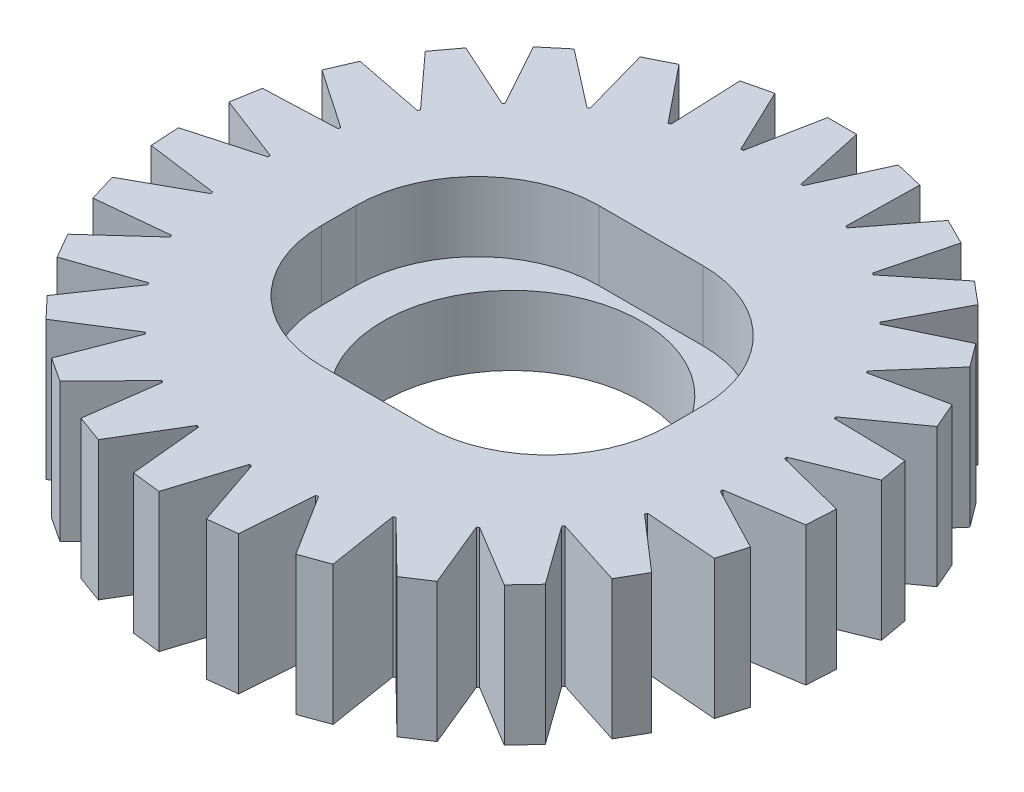
SolidWorks part; units mm, degrees
ref_plane "Front Plane" through (0, 0, 0) normal (0, 0, 1) x (1, 0, 0)
ref_plane "Top Plane" through (0, 0, 0) normal (0, 1, 0) x (1, 0, 0)
ref_plane "Right Plane" through (0, 0, 0) normal (1, 0, 0) x (0, 0, -1)
sketch "Sketch2" plane through (0, 0, 0) normal (0, 1, 0) x (1, 0, 0)
  line L0 (0, 7.5) -> (0, -22.3339) construction
  line L1 (7.5, 0) -> (-25.2541, 0) construction
  circle A0 centre (0, 0) radius 7.5
  dimension "D1" = 15
extrude "Boss-Extrude1" add sketch "Sketch2" along normal blind 4
sketch "Sketch3" plane through (0, 4, 0) normal (0, 1, 0) x (1, 0, 0)
  line L1 (-5, 4) -> (5, 4)
  line L2 (-5, 4) -> (-5, -4)
  line L3 (-5, -4) -> (5, -4)
  line L4 (5, 4) -> (5, -4)
  line L5 (-5, 4) -> (5, -4) construction
  line L6 (-5, -4) -> (5, 4) construction
  point P0 (0, 0)
  dimension "D1" = 10
  dimension "D2" = 8
extrude "Cut-Extrude1" cut sketch "Sketch3" against normal blind 2
fillet "Fillet1" radius 3.5 4 edges at (-5, 3, 4) (5, 3, 4) (-5, 3, -4) (5, 3, -4)
sketch "Sketch4" plane through (0, 2, 0) normal (0, 1, 0) x (1, 0, 0)
  line L1 (1.5, 4) -> (-1.5, 4) construction
  line L2 (0, 0) -> (0, -17.2909) construction
  circle A0 centre (0, 0) radius 3.725
  dimension "D1" = 7.45
  dimension "D3" = 4
extrude "Cut-Extrude2" cut sketch "Sketch4" against normal through all
ref_plane "Plane1" through (0, 4, 0) normal (0, 1, 0) x (1, 0, 0)
sketch "Sketch5" plane through (0, 4, 0) normal (0, 1, 0) x (1, 0, 0)
  line L0 (0, 0) -> (0, 13.0768) construction
  line L1 (0, 0) -> (17.6113, 0) construction
  line L2 (-0.7986, 7.4367) -> (-0.3997, 9.4923)
  line L3 (-0.3997, 9.4923) -> (0.4369, 9.4923)
  line L4 (0.4369, 9.4923) -> (0.8817, 7.4367)
  line L5 (0.8817, 7.4367) -> (-0.7986, 7.4367)
  line L6 (2.6142, 9.1356) -> (2.573, 7.0329)
  line L7 (0.938, 7.4204) -> (1.8001, 9.3286)
  line L8 (1.8001, 9.3286) -> (2.6142, 9.1356)
  line L9 (2.573, 7.0329) -> (0.938, 7.4204)
  line L10 (4.6505, 8.2865) -> (4.1255, 6.25)
  line L11 (2.624, 7.0041) -> (3.9029, 8.662)
  line L12 (3.9029, 8.662) -> (4.6505, 8.2865)
  line L13 (4.1255, 6.25) -> (2.624, 7.0041)
  line L14 (6.4362, 6.9907) -> (5.4557, 5.1301)
  line L15 (4.1685, 6.2102) -> (5.7953, 7.5284)
  line L16 (5.7953, 7.5284) -> (6.4362, 6.9907)
  line L17 (5.4557, 5.1301) -> (4.1685, 6.2102)
  line L18 (7.8748, 5.318) -> (6.4917, 3.7336)
  line L19 (5.4883, 5.0814) -> (7.3753, 5.989)
  line L20 (7.3753, 5.989) -> (7.8748, 5.318)
  line L21 (6.4917, 3.7336) -> (5.4883, 5.0814)
  line L22 (8.889, 3.3586) -> (7.1777, 2.1359)
  line L23 (6.5122, 3.6788) -> (8.5576, 4.1267)
  line L24 (8.5576, 4.1267) -> (8.889, 3.3586)
  line L25 (7.1777, 2.1359) -> (6.5122, 3.6788)
  line L26 (9.4239, 1.2181) -> (7.4768, 0.423)
  line L27 (7.1851, 2.0778) -> (9.2786, 2.042)
  line L28 (9.2786, 2.042) -> (9.4239, 1.2181)
  line L29 (7.4768, 0.423) -> (7.1851, 2.0778)
  line L30 (9.4508, -0.9881) -> (7.3729, -1.3126)
  line L31 (7.4706, 0.3648) -> (9.4994, -0.1529)
  line L32 (9.4994, -0.1529) -> (9.4508, -0.9881)
  line L33 (7.3729, -1.3126) -> (7.4706, 0.3648)
  line L34 (8.9682, -3.1409) -> (6.8714, -2.9776)
  line L35 (7.3533, -1.3679) -> (9.2081, -2.3395)
  line L36 (9.2081, -2.3395) -> (8.9682, -3.1409)
  line L37 (6.8714, -2.9776) -> (7.3533, -1.3679)
  line L38 (8.0021, -5.1245) -> (5.9995, -4.482)
  line L39 (6.8397, -3.0268) -> (8.4204, -4.4)
  line L40 (8.4204, -4.4) -> (8.0021, -5.1245)
  line L41 (5.9995, -4.482) -> (6.8397, -3.0268)
  line L42 (6.6046, -6.8318) -> (4.8042, -5.7447)
  line L43 (5.9573, -4.5225) -> (7.1787, -6.2232)
  line L44 (7.1787, -6.2232) -> (6.6046, -6.8318)
  line L45 (4.8042, -5.7447) -> (5.9573, -4.5225)
  line L46 (4.8511, -8.1707) -> (3.3499, -6.6978)
  line L47 (4.7537, -5.7745) -> (5.55, -7.711)
  line L48 (5.55, -7.711) -> (4.8511, -8.1707)
  line L49 (3.3499, -6.6978) -> (4.7537, -5.7745)
  line L50 (2.836, -9.0692) -> (1.715, -7.2898)
  line L51 (3.2939, -6.7151) -> (3.6222, -8.7831)
  line L52 (3.6222, -8.7831) -> (2.836, -9.0692)
  line L53 (1.715, -7.2898) -> (3.2939, -6.7151)
  line L54 (0.6681, -9.4788) -> (-0.0124, -7.4888)
  line L55 (1.6565, -7.2937) -> (1.499, -9.3817)
  line L56 (1.499, -9.3817) -> (0.6681, -9.4788)
  line L57 (-0.0124, -7.4888) -> (1.6565, -7.2937)
  line L58 (-1.5359, -9.3774) -> (-1.7391, -7.2841)
  line L59 (-0.0702, -7.4791) -> (-0.705, -9.4745)
  line L60 (-0.705, -9.4745) -> (-1.5359, -9.3774)
  line L61 (-1.7391, -7.2841) -> (-0.0702, -7.4791)
  line L62 (-3.6571, -8.7704) -> (-3.3721, -6.6866)
  line L63 (-1.7931, -7.2613) -> (-2.8709, -9.0565)
  line L64 (-2.8709, -9.0565) -> (-3.6571, -8.7704)
  line L65 (-3.3721, -6.6866) -> (-1.7931, -7.2613)
  line L66 (-5.5811, -7.6906) -> (-4.8232, -5.7288)
  line L67 (-3.4193, -6.6521) -> (-4.8821, -8.1503)
  line L68 (-4.8821, -8.1503) -> (-5.5811, -7.6906)
  line L69 (-4.8232, -5.7288) -> (-3.4193, -6.6521)
  line L70 (-7.2042, -6.1962) -> (-6.0143, -4.462)
  line L71 (-4.8613, -5.6842) -> (-6.6301, -6.8047)
  line L72 (-6.6301, -6.8047) -> (-7.2042, -6.1962)
  line L73 (-6.0143, -4.462) -> (-4.8613, -5.6842)
  line L74 (-8.439, -4.3678) -> (-6.8812, -2.9548)
  line L75 (-6.0411, -4.4099) -> (-8.0207, -5.0923)
  line L76 (-8.0207, -5.0923) -> (-8.439, -4.3678)
  line L77 (-6.8812, -2.9548) -> (-6.0411, -4.4099)
  line L78 (-9.2188, -2.3039) -> (-7.3772, -1.2882)
  line L79 (-6.8953, -2.8979) -> (-8.9788, -3.1053)
  line L80 (-8.9788, -3.1053) -> (-9.2188, -2.3039)
  line L81 (-7.3772, -1.2882) -> (-6.8953, -2.8979)
  line L82 (-9.5016, -0.1158) -> (-7.4754, 0.4478)
  line L83 (-7.3777, -1.2296) -> (-9.453, -0.951)
  line L84 (-9.453, -0.951) -> (-9.5016, -0.1158)
  line L85 (-7.4754, 0.4478) -> (-7.3777, -1.2296)
  line L86 (-9.2722, 2.0785) -> (-7.1706, 2.1597)
  line L87 (-7.4624, 0.5049) -> (-9.4175, 1.2547)
  line L88 (-9.4175, 1.2547) -> (-9.2722, 2.0785)
  line L89 (-7.1706, 2.1597) -> (-7.4624, 0.5049)
  line L90 (-8.5429, 4.1608) -> (-6.4793, 3.7551)
  line L91 (-7.1448, 2.2123) -> (-8.8743, 3.3927)
  line L92 (-8.8743, 3.3927) -> (-8.5429, 4.1608)
  line L93 (-6.4793, 3.7551) -> (-7.1448, 2.2123)
  line L94 (-7.3531, 6.0188) -> (-5.4386, 5.1481)
  line L95 (-6.442, 3.8003) -> (-7.8527, 5.3478)
  line L96 (-7.8527, 5.3478) -> (-7.3531, 6.0188)
  line L97 (-5.4386, 5.1481) -> (-6.442, 3.8003)
  line L98 (-5.7668, 7.5523) -> (-4.1048, 6.2636)
  line L99 (-5.392, 5.1835) -> (-6.4077, 7.0146)
  line L100 (-6.4077, 7.0146) -> (-5.7668, 7.5523)
  line L101 (-4.1048, 6.2636) -> (-5.392, 5.1835)
  line L102 (-3.8697, 8.6787) -> (-2.5496, 7.0414)
  line L103 (-4.0512, 6.2873) -> (-4.6173, 8.3032)
  line L104 (-4.6173, 8.3032) -> (-3.8697, 8.6787)
  line L105 (-2.5496, 7.0414) -> (-4.0512, 6.2873)
  line L106 (-1.764, 9.3371) -> (-0.8571, 7.4396)
  line L107 (-2.4921, 7.0521) -> (-2.578, 9.1442)
  line L108 (-2.578, 9.1442) -> (-1.764, 9.3371)
  line L109 (-0.8571, 7.4396) -> (-2.4921, 7.0521)
  point P126 (0, 0)
  dimension "D1" = 27
extrude "Boss-Extrude2" add sketch "Sketch5" against normal blind 4
